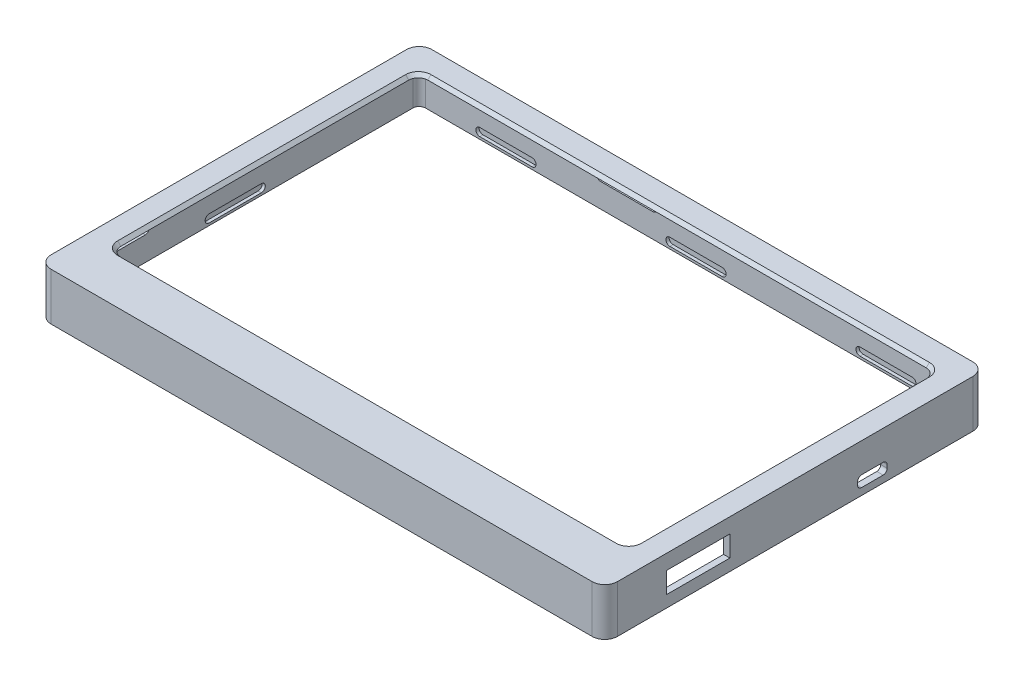
SolidWorks part; units mm, degrees
ref_plane "前基準面" through (0, 0, 0) normal (0, 0, 1) x (1, 0, 0)
ref_plane "上基準面" through (0, 0, 0) normal (0, 1, 0) x (1, 0, 0)
ref_plane "右基準面" through (0, 0, 0) normal (1, 0, 0) x (0, 0, -1)
sketch "草圖1" plane through (0, 0, 0) normal (0, 1, 0) x (1, 0, 0)
  line L1 (-89.4, 60.1) -> (89.4, 60.1)
  line L2 (-89.4, 60.1) -> (-89.4, -60.1)
  line L3 (-89.4, -60.1) -> (89.4, -60.1)
  line L4 (89.4, 60.1) -> (89.4, -60.1)
  line L5 (-89.4, 60.1) -> (89.4, -60.1) construction
  line L6 (-89.4, -60.1) -> (89.4, 60.1) construction
  point P0 (0, 0)
  dimension "D1" = 120.2
  dimension "D2" = 178.8
extrude "填料-伸長1" add sketch "草圖1" along normal blind 16
fillet "圓角1" radius 4 4 edges at (89.4, 8, -60.1) (89.4, 8, 60.1) (-89.4, 8, 60.1) (-89.4, 8, -60.1)
shell "薄殼1" thickness 2 removed face at (0, 0, 0)
sketch "草圖4" plane through (0, 16, 0) normal (0, 1, 0) x (1, 0, 0)
  line L0 (85.4, 60.1) -> (-85.4, 60.1) construction
  line L1 (-89.4107, 60.1) -> (89.4107, 60.1)
  line L2 (-89.4107, 60.1) -> (-89.4107, -60.1)
  line L3 (-89.4107, -60.1) -> (89.4107, -60.1)
  line L4 (89.4107, 60.1) -> (89.4107, -60.1)
  line L5 (-89.4107, 60.1) -> (89.4107, -60.1) construction
  line L6 (-89.4107, -60.1) -> (89.4107, 60.1) construction
  point P0 (0, 0)
extrude "除料-伸長2" cut sketch "草圖4" against normal blind 1
sketch "草圖2" plane through (0, 15, 0) normal (0, 1, 0) x (1, 0, 0)
  line L1 (-81.7, 52.1) -> (81.7, 52.1)
  line L2 (-81.7, 52.1) -> (-81.7, -44.82)
  line L3 (-81.7, -44.82) -> (81.7, -44.82)
  line L4 (81.7, 52.1) -> (81.7, -44.82)
  line L5 (-81.7, 52.1) -> (81.7, -44.82) construction
  line L6 (-81.7, -44.82) -> (81.7, 52.1) construction
  line L7 (0, 60.1) -> (0, -60.1) construction
  line L9 (85.4, 60.1) -> (-85.4, 60.1) construction
  line L10 (-85.4, -60.1) -> (85.4, -60.1) construction
  point P0 (0, 3.64)
  dimension "D1" = 8
  dimension "D2" = 163.4
  dimension "D3" = 96.92
extrude "除料-伸長1" cut sketch "草圖2" against normal up to surface (1 mm away) up to face at (0, 14, 0)
fillet "圓角2" radius 3 4 edges at (81.7, 14.5, -52.1) (81.7, 14.5, 44.82) (-81.7, 14.5, 44.82) (-81.7, 14.5, -52.1)
chamfer "導角1" distance 1 angle 45 8 edges at (0, 15, 44.82) (80.8213, 15, 43.9413) (-80.8213, 15, 43.9413) (81.7, 15, -3.64) (-81.7, 15, -3.64) (80.8213, 15, -51.2213) (-80.8213, 15, -51.2213) (0, 15, -52.1)
sketch "草圖5" plane through (0, 0, -58.1) normal (0, 0, 1) x (1, 0, 0)
  line L0 (-85.4, 15) -> (85.4, 15) construction
  line L1 (-11.85, 6.81) -> (-31.85, 6.81)
  line L2 (-11.85, 6.81) -> (-11.85, 10.81)
  line L3 (-11.85, 10.81) -> (-31.85, 10.81)
  line L4 (-31.85, 6.81) -> (-31.85, 10.81)
  line L5 (-31.85, 8.81) -> (-11.85, 8.81) construction
  line L6 (-30.1, 8.81) -> (-13.6, 8.81) construction
  line L7 (-30.1, 10.06) -> (-13.6, 10.06)
  line L8 (-30.1, 7.56) -> (-13.6, 7.56)
  arc A0 (-30.1, 10.06) -> (-30.1, 7.56) centre (-30.1, 8.81) ccw
  arc A1 (-13.6, 7.56) -> (-13.6, 10.06) centre (-13.6, 8.81) ccw
  point P12 (-21.85, 8.81)
  dimension "D1" = 11.85
  dimension "D2" = 4.19
  dimension "D3" = 4
  dimension "D4" = 20
  dimension "D5" = 16.5
  dimension "D6" = 2.5
extrude "除料-伸長3" cut sketch "草圖5" against normal blind 1 contours L8 A1 L7 A0 | L8 A0 L7 A1 region at (-21.85, 8.81, -58.1)
sketch "草圖6" plane through (-87.4, 0, 0) normal (1, 0, 0) x (0, 0, -1)
  line L0 (-56.1, 15) -> (56.1, 15) construction
  line L1 (-26.64, 6.81) -> (-46.64, 6.81)
  line L2 (-26.64, 6.81) -> (-26.64, 10.81)
  line L3 (-26.64, 10.81) -> (-46.64, 10.81)
  line L4 (-46.64, 6.81) -> (-46.64, 10.81)
  line L5 (-26.64, 8.81) -> (-46.64, 8.81) construction
  line L6 (-28.39, 8.81) -> (-44.89, 8.81) construction
  line L7 (-28.39, 7.56) -> (-44.89, 7.56)
  line L8 (-28.39, 10.06) -> (-44.89, 10.06)
  arc A0 (-28.39, 7.56) -> (-28.39, 10.06) centre (-28.39, 8.81) ccw
  arc A1 (-44.89, 10.06) -> (-44.89, 7.56) centre (-44.89, 8.81) ccw
  point P10 (-36.64, 8.81)
  dimension "D1" = 4.19
  dimension "D2" = 20
  dimension "D3" = 4
  dimension "D4" = 16.5
  dimension "D5" = 2.5
  dimension "D6" = 26.64
extrude "除料-伸長4" cut sketch "草圖6" against normal blind 1 contours L8 A1 L7 A0 region at (-87.4, 8.81, 36.64)
sketch "草圖7" plane through (0, 0, 58.1) normal (0, 0, -1) x (-1, 0, 0)
  line L0 (-85.4, 15) -> (85.4, 15) construction
  line L1 (-57.03, 10.81) -> (-37.03, 10.81)
  line L2 (-57.03, 10.81) -> (-57.03, 6.81)
  line L3 (-57.03, 6.81) -> (-37.03, 6.81)
  line L4 (-37.03, 10.81) -> (-37.03, 6.81)
  line L5 (-57.03, 8.81) -> (-37.03, 8.81) construction
  line L6 (-55.28, 8.81) -> (-38.78, 8.81) construction
  line L7 (-55.28, 10.06) -> (-38.78, 10.06)
  line L8 (-55.28, 7.56) -> (-38.78, 7.56)
  line L9 (0, 0) -> (0, 15) construction
  line L10 (-57.03, 10.81) -> (-37.03, 10.81)
  line L11 (-57.03, 6.81) -> (-37.03, 6.81)
  line L12 (57.03, 8.81) -> (37.03, 8.81) construction
  line L13 (57.03, 6.81) -> (37.03, 6.81)
  line L14 (57.03, 10.81) -> (37.03, 10.81)
  line L15 (37.03, 10.81) -> (37.03, 6.81)
  line L16 (57.03, 6.81) -> (37.03, 6.81)
  line L17 (57.03, 10.81) -> (57.03, 6.81)
  line L18 (57.03, 10.81) -> (37.03, 10.81)
  line L19 (55.28, 8.81) -> (38.78, 8.81) construction
  line L20 (55.28, 10.06) -> (38.78, 10.06)
  line L21 (55.28, 7.56) -> (38.78, 7.56)
  arc A0 (-55.28, 10.06) -> (-55.28, 7.56) centre (-55.28, 8.81) ccw
  arc A1 (-38.78, 7.56) -> (-38.78, 10.06) centre (-38.78, 8.81) ccw
  arc A2 (55.28, 10.06) -> (55.28, 7.56) centre (55.28, 8.81) cw
  arc A3 (38.78, 7.56) -> (38.78, 10.06) centre (38.78, 8.81) cw
  point P4 (-37.03, 8.81)
  point P12 (-47.03, 8.81)
  point P27 (47.03, 8.81)
  dimension "D1" = 20
  dimension "D2" = 4
  dimension "D3" = 37.03
  dimension "D4" = 4.19
  dimension "D5" = 16.5
  dimension "D6" = 2.5
extrude "除料-伸長5" cut sketch "草圖7" against normal blind 1 contours L8 A1 L7 A0 | A3 L21 A2 L20 region at (47.03, 8.81, 58.1) region at (-47.03, 8.81, 58.1)
sketch "草圖8" plane through (87.4, 0, 0) normal (-1, 0, 0) x (0, 0, 1)
  line L0 (-56.1, 15) -> (56.1, 15) construction
  line L1 (43.6, 6.81) -> (53.6, 6.81)
  line L2 (43.6, 6.81) -> (43.6, 10.81)
  line L3 (43.6, 10.81) -> (53.6, 10.81)
  line L4 (53.6, 6.81) -> (53.6, 10.81)
  line L5 (60.1, 15) -> (60.1, 0) construction
  line L6 (43.6, 8.81) -> (53.6, 8.81) construction
  line L7 (44.85, 8.81) -> (52.35, 8.81) construction
  line L8 (44.85, 10.06) -> (52.35, 10.06)
  line L9 (44.85, 7.56) -> (52.35, 7.56)
  arc A0 (44.85, 10.06) -> (44.85, 7.56) centre (44.85, 8.81) ccw
  arc A1 (52.35, 7.56) -> (52.35, 10.06) centre (52.35, 8.81) ccw
  point P12 (48.6, 8.81)
  dimension "D1" = 10
  dimension "D2" = 4
  dimension "D3" = 4.19
  dimension "D4" = 6.5
  dimension "D5" = 2.5
  dimension "D6" = 7.5
extrude "除料-伸長6" cut sketch "草圖8" against normal blind 1 contours A1 L8 A0 L9 region at (87.4, 8.81, 48.6)
sketch "草圖9" plane through (89.4, 0, 0) normal (1, 0, 0) x (0, 0, -1)
  line L1 (27.79, 2.18) -> (20.99, 2.18)
  line L2 (29.04, 3.43) -> (29.04, 4.43)
  line L3 (27.79, 5.68) -> (20.99, 5.68)
  line L4 (19.74, 3.43) -> (19.74, 4.43)
  line L5 (29.04, 2.18) -> (19.74, 5.68) construction
  line L6 (29.04, 5.68) -> (19.74, 2.18) construction
  line L8 (60.1, 15) -> (60.1, 0) construction
  line L9 (-56.1, 15) -> (56.1, 15) construction
  arc A0 (20.99, 5.68) -> (19.74, 4.43) centre (20.99, 4.43) ccw
  arc A1 (20.99, 2.18) -> (19.74, 3.43) centre (20.99, 3.43) cw
  arc A2 (27.79, 2.18) -> (29.04, 3.43) centre (27.79, 3.43) ccw
  arc A3 (29.04, 4.43) -> (27.79, 5.68) centre (27.79, 4.43) ccw
  point P0 (24.39, 3.93)
  dimension "D5" = 1.25
  dimension "D1" = 35.71
  dimension "D2" = 11.07
  dimension "D3" = 9.3
  dimension "D4" = 3.5
extrude "除料-伸長7" cut sketch "草圖9" against normal up to next
sketch "草圖10" plane through (89.4, 0, 0) normal (1, 0, 0) x (0, 0, -1)
  line L0 (-60.1, 0) -> (-60.1, 15) construction
  line L1 (-40.6, 10.3) -> (-20.6, 10.3)
  line L2 (-40.6, 10.3) -> (-40.6, 3.7)
  line L3 (-40.6, 3.7) -> (-20.6, 3.7)
  line L4 (-20.6, 10.3) -> (-20.6, 3.7)
  line L5 (-40.6, 10.3) -> (-20.6, 3.7) construction
  line L6 (-40.6, 3.7) -> (-20.6, 10.3) construction
  line L7 (-56.1, 15) -> (56.1, 15) construction
  point P0 (-30.6, 7)
  dimension "D1" = 20
  dimension "D2" = 6.6
  dimension "D3" = 19.5
  dimension "D4" = 4.7
extrude "除料-伸長8" cut sketch "草圖10" against normal up to next
sketch "草圖11" plane through (0, 0, -58.1) normal (0, 0, 1) x (1, 0, 0)
  line L0 (-8.25, 2) -> (8.25, 2) construction
  line L1 (-8.25, 3.25) -> (8.25, 3.25)
  line L2 (-8.25, 0.75) -> (8.25, 0.75)
  line L3 (-85.4, 0) -> (85.4, 0) construction
  line L4 (51.75, 2) -> (68.25, 2) construction
  line L5 (51.75, 3.25) -> (68.25, 3.25)
  line L6 (51.75, 0.75) -> (68.25, 0.75)
  line L7 (-68.25, 2) -> (-51.75, 2) construction
  line L8 (-68.25, 3.25) -> (-51.75, 3.25)
  line L9 (-68.25, 0.75) -> (-51.75, 0.75)
  arc A0 (-8.25, 3.25) -> (-8.25, 0.75) centre (-8.25, 2) ccw
  arc A1 (8.25, 0.75) -> (8.25, 3.25) centre (8.25, 2) ccw
  arc A2 (51.75, 3.25) -> (51.75, 0.75) centre (51.75, 2) ccw
  arc A3 (68.25, 0.75) -> (68.25, 3.25) centre (68.25, 2) ccw
  arc A4 (-68.25, 3.25) -> (-68.25, 0.75) centre (-68.25, 2) ccw
  arc A5 (-51.75, 0.75) -> (-51.75, 3.25) centre (-51.75, 2) ccw
  point P2 (0, 2)
  point P13 (60, 2)
  point P20 (-60, 2)
  dimension "D1" = 16.5
  dimension "D2" = 2.5
  dimension "D3" = 2
  dimension "D4" = 2
  dimension "D5" = 2
extrude "除料-伸長9" cut sketch "草圖11" against normal blind 1
ref_plane "平面1" through (0, 0, 0) normal (0, 0, 1) x (1, 0, 0)
mirror "鏡射1" about plane through (0, 0, 0) normal (0, 0, 1) of "除料-伸長9"
ref_plane "平面2" through (0, 0, 0) normal (-1, 0, 0) x (0, 0, 1)
sketch "草圖12" plane through (-87.4, 0, 0) normal (1, 0, 0) x (0, 0, -1)
  line L0 (-8.25, 2) -> (8.25, 2) construction
  line L1 (-8.25, 3.25) -> (8.25, 3.25)
  line L2 (-8.25, 0.75) -> (8.25, 0.75)
  line L3 (-56.1, 0) -> (56.1, 0) construction
  arc A0 (-8.25, 3.25) -> (-8.25, 0.75) centre (-8.25, 2) ccw
  arc A1 (8.25, 0.75) -> (8.25, 3.25) centre (8.25, 2) ccw
  point P2 (0, 2)
  dimension "D1" = 16.5
  dimension "D2" = 2.5
  dimension "D3" = 2
extrude "除料-伸長10" cut sketch "草圖12" against normal blind 1
mirror "鏡射2" about plane through (0, 0, 0) normal (-1, 0, 0) of "除料-伸長10"
sketch "草圖13" plane through (0, 14, 0) normal (0, -1, 0) x (1, 0, 0)
  line L1 (-85.4, 58.1) -> (-15, 58.1)
  line L2 (-87.4, 56.1) -> (-87.4, -56.1)
  line L3 (-85.4, -58.1) -> (85.4, -58.1)
  line L4 (87.4, 56.1) -> (87.4, -56.1)
  line L5 (-87.4, 58.1) -> (87.4, -58.1) construction
  line L6 (-87.4, -58.1) -> (87.4, 58.1) construction
  line L8 (87.4, 56.1) -> (87.4, -56.1) construction
  line L9 (85.4, -58.1) -> (-85.4, -58.1) construction
  line L10 (15, 58.1) -> (15, 55.965)
  line L11 (85.325, -55.705) -> (-85.325, -55.705)
  line L12 (85.325, -55.705) -> (85.325, 55.965)
  line L13 (85.325, 55.965) -> (15, 55.965)
  line L14 (-85.325, -55.705) -> (-85.325, 55.965)
  line L15 (85.325, -55.705) -> (-85.325, 55.965) construction
  line L16 (85.325, 55.965) -> (-85.325, -55.705) construction
  line L17 (0, 58.1) -> (0, 55.65) construction
  line L18 (-15, 58.1) -> (-15, 55.965)
  line L19 (15, 58.1) -> (85.4, 58.1)
  line L20 (-15, 55.965) -> (-85.325, 55.965)
  arc A0 (-87.4, -56.1) -> (-85.4, -58.1) centre (-85.4, -56.1) ccw
  arc A1 (-85.4, 58.1) -> (-87.4, 56.1) centre (-85.4, 56.1) ccw
  arc A2 (85.4, 58.1) -> (87.4, 56.1) centre (85.4, 56.1) cw
  arc A3 (85.4, -58.1) -> (87.4, -56.1) centre (85.4, -56.1) ccw
  point P0 (0, 0)
  point P9 (0, -58.1)
  point P24 (0, 0.13)
  dimension "D1" = 2
  dimension "D2" = 170.65
  dimension "D3" = 111.67
  dimension "D4" = 58.23
  dimension "D5" = 15
extrude "填料-伸長2" add sketch "草圖13" along normal blind 1
equation "\"ㄉ\"=4"
equation "\"ㄉ0\"=21"
equation "\"ㄉㄢ\"=21"
